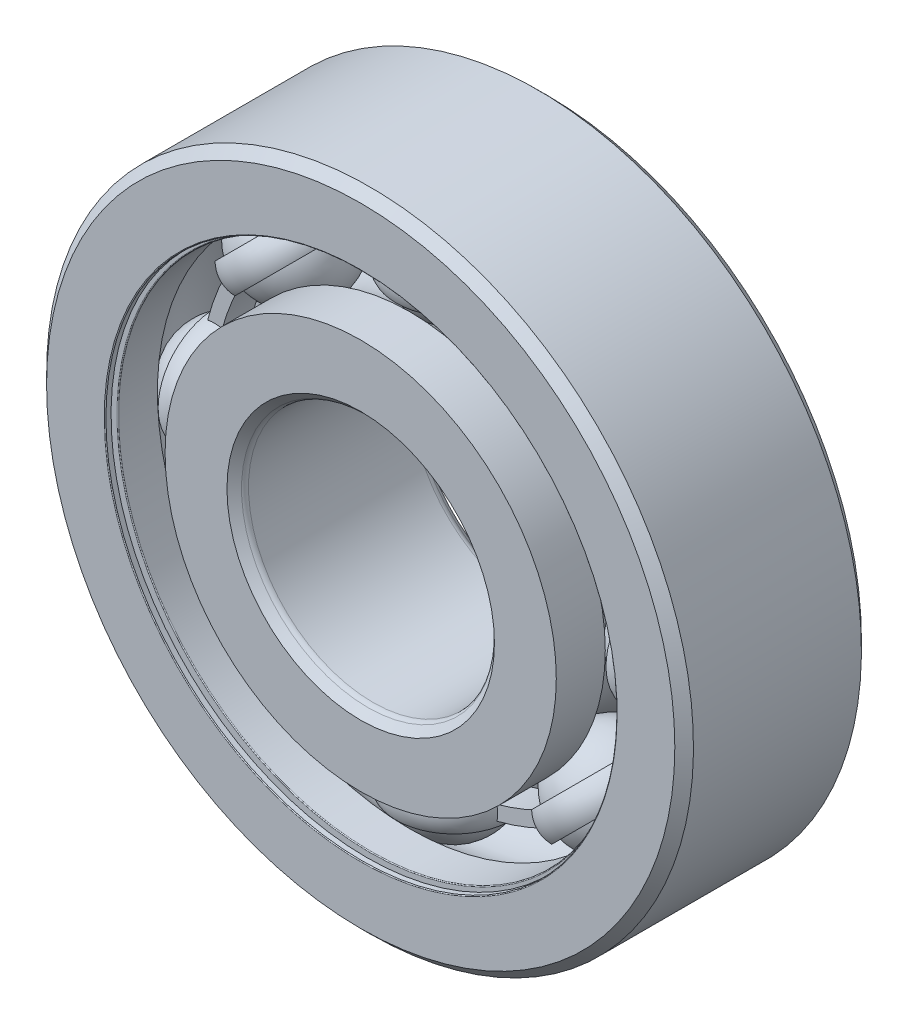
SolidWorks part; units mm, degrees
ref_plane "Front Plane" through (0, 0, 0) normal (0, 0, 1) x (1, 0, 0)
ref_plane "Top Plane" through (0, 0, 0) normal (0, 1, 0) x (1, 0, 0)
ref_plane "Right Plane" through (0, 0, 0) normal (1, 0, 0) x (0, 0, -1)
sketch "Sketch1" plane through (0, 0, 0) normal (0, 0, 1) x (1, 0, 0)
  line L0 (-26, 0) -> (26, 0) construction
  line L1 (-10, 0) -> (10, 0) construction
  circle A0 centre (0, 0) radius 10 construction
  circle A1 centre (0, 0) radius 26 construction
  point P3 (0, 0)
  point P6 (0, 0)
  point P7 (0, -10)
  point P11 (0, -26)
  point P12 (0, 10)
  point P13 (0, 26)
  dimension "OD" = 52
  dimension "ID" = 20
sketch "Sketch2" plane through (0, 0, 0) normal (1, 0, 0) x (0, 0, -1)
  line L0 (-7.5, 26) -> (7.5, 26) construction
  line L1 (0, 26) -> (0, -26) construction
  line L2 (6.75, 26) -> (-6.75, 26)
  line L3 (-6.75, 26) -> (-7.5, 25.25)
  line L4 (-7.5, 25.25) -> (-7.5, 20.2769)
  line L5 (-7.5, 20.2769) -> (-3.5625, 20.2769)
  line L6 (7.5, 20.2769) -> (3.5625, 20.2769)
  line L7 (7.5, 25.25) -> (7.5, 20.2769)
  line L8 (6.75, 26) -> (7.5, 25.25)
  line L9 (0, 26) -> (0, 18) construction
  line L10 (0, 18) -> (0, 10) construction
  line L11 (0, 26) -> (0, -26) construction
  line L12 (-7.5, 0) -> (7.5, 0) construction
  line L13 (7.5, 10) -> (-7.5, 10) construction
  line L14 (0, 22.228) -> (0, 13.772) construction
  line L15 (-7.5, -10) -> (7.5, -10) construction
  line L16 (-7.5, -10) -> (-7.5, 10) construction
  line L17 (7.5, 26) -> (7.5, -26) construction
  arc A0 (-3.5625, 20.2769) -> (3.5625, 20.2769) centre (0, 18) cw
  circle A1 centre (0, 18) radius 4.228 construction
  point P14 (0, 10)
  point P17 (0, 0)
  point P21 (0, 26)
  point P29 (0, 10)
  point P30 (0, -10)
  point P35 (0, 22.228)
  dimension "Approx. Ball Dia." = 8.456
  dimension "Width" = 15
  dimension "D1" = 45
  dimension "D2" = 0.75
  dimension "D3" = 7.125
  dimension "D4" = 2.2769
  dimension "For Shaft Diameter" = 20
  dimension "For Housing ID" = 52
sketch "Sketch3" plane through (0, 0, 0) normal (1, 0, 0) x (0, 0, -1)
  line L0 (6.75, 26) -> (7.5, 25.25) construction
  line L1 (7.5, 25.25) -> (7.5, 20.2769) construction
  line L2 (7.5, 20.2769) -> (3.5625, 20.2769) construction
  line L3 (-7.5, 20.2769) -> (-3.5625, 20.2769) construction
  line L4 (-7.5, 25.25) -> (-7.5, 20.2769) construction
  line L5 (-6.75, 26) -> (-7.5, 25.25) construction
  line L6 (6.75, 26) -> (-6.75, 26) construction
  line L7 (6.75, 26) -> (7.5, 25.25)
  line L8 (7.5, 25.25) -> (7.5, 20.2769)
  line L9 (7.5, 20.2769) -> (3.5625, 20.2769)
  line L10 (-7.5, 20.2769) -> (-3.5625, 20.2769)
  line L11 (-7.5, 25.25) -> (-7.5, 20.2769)
  line L12 (-6.75, 26) -> (-7.5, 25.25)
  line L13 (6.75, 26) -> (-6.75, 26)
  arc A0 (3.5625, 20.2769) -> (-3.5625, 20.2769) centre (0, 18) ccw construction
  arc A1 (3.5625, 20.2769) -> (-3.5625, 20.2769) centre (0, 18) ccw
revolve "Revolve1" add sketch "Sketch3" angle 360 about L12
sketch "Sketch8" plane through (0, 0, 0) normal (1, 0, 0) x (0, 0, -1)
  line L0 (-7.5, 20.2769) -> (-3.5625, 20.2769) construction
  line L1 (-7.02, 20.2769) -> (-6.75, 20.2769)
  line L2 (-7.02, 20.2769) -> (-7.02, 22.1846) construction
  line L3 (-7.02, 22.1846) -> (-6.75, 22.1846)
  line L4 (-6.75, 20.2769) -> (-6.75, 22.1846)
  line L5 (7.5, 20.2769) -> (3.5625, 20.2769) construction
  line L6 (6.75, 20.2769) -> (7.02, 20.2769)
  line L7 (6.75, 20.2769) -> (6.75, 22.1846)
  line L8 (6.75, 22.1846) -> (7.02, 22.1846)
  line L9 (7.02, 20.2769) -> (7.02, 22.1846) construction
  line L10 (-6.75, 22.1846) -> (6.75, 22.1846) construction
  line L11 (0, 26) -> (0, -26) construction
  line L12 (-7.02, 22.1846) -> (-7.02, 24.0923) construction
  line L13 (-7.02, 24.0923) -> (-7.02, 26) construction
  line L14 (-7.5, 26) -> (7.5, 26) construction
  line L15 (-7.02, 20.2769) -> (-7.5, 20.2769)
  line L16 (-7.5, 20.2769) -> (-7.5, 20.5469)
  line L17 (-7.5, 25.25) -> (-7.5, 20.2769) construction
  line L18 (-7.5, 20.5469) -> (-7.02, 20.5469)
  line L19 (-7.02, 20.5469) -> (-7.02, 22.1846)
  line L20 (7.02, 20.2769) -> (7.5, 20.2769)
  line L21 (7.5, 20.2769) -> (7.5, 20.5469)
  line L22 (7.5, 25.25) -> (7.5, 20.2769) construction
  line L23 (7.5, 20.5469) -> (7.02, 20.5469)
  line L24 (7.02, 20.5469) -> (7.02, 22.1846)
  point P12 (0, 22.1846)
  dimension "D1" = 13.5
  dimension "D2" = 0.27
revolve "Cut-Revolve1" cut sketch "Sketch8" angle 360 about L12
sketch "Sketch4" plane through (0, 0, 0) normal (1, 0, 0) x (0, 0, -1)
  line L0 (0, 26) -> (0, -26) construction
  line L1 (0, 26) -> (0, -26) construction
  line L2 (-6.75, 10) -> (-7.5, 10.75)
  line L3 (-7.5, 10.75) -> (-7.5, 15.7231)
  line L5 (-7.5, 15.7231) -> (-3.5625, 15.7231)
  line L6 (-6.75, 10) -> (6.75, 10)
  line L8 (6.75, 10) -> (7.5, 10.75)
  line L10 (7.5, 10.75) -> (7.5, 15.7231)
  line L11 (7.5, 15.7231) -> (3.5625, 15.7231)
  line L12 (-7.5, 25.25) -> (-7.5, 20.2769) construction
  line L13 (6.75, 26) -> (7.5, 25.25) construction
  line L15 (7.5, -25.25) -> (7.5, 25.25) construction
  line L16 (6.75, 26) -> (6.75, -26) construction
  arc A1 (3.5625, 15.7231) -> (-3.5625, 15.7231) centre (0, 18) cw
  circle A2 centre (0, 18) radius 4.228 construction
  point P1 (0, 10)
revolve "Revolve2" add sketch "Sketch4" angle 360 about L12
sketch "Sketch5" plane through (0, 0, 0) normal (1, 0, 0) x (0, 0, -1)
  line L0 (-4.228, 18) -> (4.228, 18)
  arc A2 (-4.228, 18) -> (4.228, 18) centre (0, 18) cw
  arc A3 (3.5625, 20.2769) -> (-3.5625, 20.2769) centre (0, 18) ccw construction
revolve "Revolve3" add sketch "Sketch5" angle 360 about L0
sketch "Sketch6" plane through (0, 0, 0) normal (1, 0, 0) x (0, 0, -1)
  line L0 (-3.5625, 20.2769) -> (-3.5625, 19.1385) construction
  line L1 (-3.5625, 19.1385) -> (-3.5625, 18) construction
  line L2 (-3.5625, 18) -> (-3.5625, 16.8615) construction
  line L3 (-3.5625, 16.8615) -> (-3.5625, 15.7231) construction
  line L4 (-7.5, 19.1385) -> (-6.9286, 19.1385) construction
  line L5 (-3.5625, 19.1385) -> (-3.5625, 16.8615) construction
  line L7 (-6.9286, 19.1385) -> (-6.3573, 19.1385) construction
  line L8 (-6.3573, 19.1385) -> (-5.7859, 19.1385) construction
  line L10 (0, 26) -> (0, -26) construction
  line L11 (0, 26) -> (0, -26) construction
  line L12 (-7.5, 20.2769) -> (-7.5, 19.1385) construction
  line L13 (-4.6432, 19.1385) -> (-4.0718, 19.1385) construction
  line L14 (-7.5, 25.25) -> (-7.5, -25.25) construction
  line L15 (-7.5, 19.1385) -> (-7.5, 18) construction
  line L16 (-7.5, 18) -> (-7.5, 16.8615) construction
  line L17 (-7.5, 16.8615) -> (-7.5, 15.7231) construction
  line L18 (-5.7859, 19.1385) -> (-5.2145, 19.1385) construction
  line L19 (-5.2145, 19.1385) -> (-4.6432, 19.1385) construction
  line L20 (-4.0718, 19.1385) -> (-4.6432, 19.1385)
  line L21 (-7.5, 16.8615) -> (-6.9286, 16.8615) construction
  line L22 (-6.9286, 16.8615) -> (-6.3573, 16.8615) construction
  line L23 (-6.3573, 16.8615) -> (-5.7859, 16.8615) construction
  line L24 (-5.7859, 16.8615) -> (-5.2145, 16.8615) construction
  line L25 (-5.2145, 16.8615) -> (-4.6432, 16.8615) construction
  line L26 (-4.6432, 16.8615) -> (-4.0718, 16.8615) construction
  line L27 (-4.0718, 16.8615) -> (-4.6432, 16.8615)
  line L28 (-5.2145, 19.1385) -> (-5.2145, 16.8615) construction
  line L30 (-4.9289, 19.1385) -> (-4.9289, 16.8615) construction
  circle A0 centre (0, 18) radius 4.228 construction
  arc A2 (-4.6432, 16.8615) -> (-4.6432, 19.1385) centre (-2.5176, 18) cw
  arc A3 (-4.0718, 19.1385) -> (-4.0718, 16.8615) centre (0, 18) ccw
revolve "Revolve4" add sketch "Sketch6" angle 360 about L11
sketch "Sketch7" plane through (0, 0, 0) normal (0, 0, 1) x (1, 0, 0)
  line L0 (-4.228, 18) -> (4.228, 18) construction
  line L1 (0, 13.772) -> (0, 22.228) construction
  line L2 (0, 0) -> (7.1177, 16.5329) construction
  line L8 (0, 26) -> (0, -26) construction
  line L9 (13.0752, 12.3709) -> (13.9022, 13.1533)
  line L10 (0, 26) -> (0, -26) construction
  line L11 (0, 19.1385) -> (0, 18)
  arc A1 (13.0752, 12.3709) -> (0, 18) centre (0, 0) ccw
  arc A2 (13.9022, 13.1533) -> (0, 19.1385) centre (0, 0) ccw
  dimension "D1" = 46.586
  dimension "D2" = 8.456
extrude "Boss-Extrude1" add sketch "Sketch7" along normal mid plane 2.5
pattern_circular "CirPattern1" count 8 over 360 about axis through (0, 0, 7.5) along (0, 0, -1) of bodies 104 134
pattern_circular "CirPattern2" count 8 over 360 about axis through (0, 0, 7.5) along (0, 0, -1) of "Revolve4", "Boss-Extrude1" reverse direction yes
fillet "Fillet1" radius 0.0675 4 edges at (0, -20.2769, -6.75) (0, -20.5469, -7.5) (0, -20.2769, 6.75) (0, -20.5469, 7.5)
fillet "Fillet2" radius 0.5625 2 edges at (0, -10, -6.75) (0, -10, 6.75)
ref_plane "Plane1" through (7.1177, 16.5329, 0) normal (0.3954, 0.9185, 0) x (0.9185, -0.3954, 0)
sketch "Sketch9" plane through (7.1177, 16.5329, 0) normal (0.3954, 0.9185, 0) x (0.9185, -0.3954, 0)
  line L0 (-3.2344, -1.25) -> (-3.2344, -3.75)
  line L1 (-3.2344, -3.75) -> (-1.4029, -3.75)
  line L2 (-1.4029, -3.75) -> (0, -2.5728)
  line L3 (0, -2.5728) -> (1.4029, -3.75)
  line L4 (1.4029, -3.75) -> (3.2344, -3.75)
  line L5 (3.2344, -3.75) -> (3.2344, -1.25)
  line L6 (3.2344, -1.25) -> (-3.2344, -1.25)
  line L7 (0, -1.25) -> (0, 0) construction
  line L8 (-3.2344, -1.25) -> (-3.2344, 0) construction
  dimension "D1" = 2.5
  dimension "D2" = 1.25
  dimension "D3" = 40
extrude "Boss-Extrude2" [suppressed] add sketch "Sketch9" along normal blind 3.6995 draft 15 and the other way blind 3.6995 draft 10 separate body draft outward yes other way draft outward yes
fillet "Fillet3" [suppressed] radius 0.75
mirror "Mirror1" [suppressed] about plane through (0, 0, 0) normal (0, 0, 1) of bodies 149
pattern_circular "CirPattern3" [suppressed] count 8 over 360 about axis through (0, 0, 7.5) along (0, 0, -1) of bodies 158 149
equation "\"D2@Sketch2\" = \"Width@Sketch2\" * .05"
equation "\"D3@Sketch2\"=\"Width@Sketch2\" * .475"
equation "\"D4@Sketch2\" =  (  (  ( \"OD@Sketch1\" - \"Width@Sketch2\" )  / 2 )  / 3.25 )  / 2.5"
equation "\"D1@Boss-Extrude1\" = \"Width@Sketch2\" / 6"
equation "\"D1@Sketch8\"=\"Width@Sketch2\"*.9"
equation "\"D2@Sketch8\"=\"D1@Sketch8\"*.02"
equation "\"D1@Fillet1\" = \"D2@Sketch8\" * .25"
equation "\"D1@Fillet2\" = \"D2@Sketch2\" * .75"
equation "\"Approx No of Balls\"= ( pi * \"OD@Sketch1\" ) * .4 / \"Approx. Ball Dia.@Sketch2\""
equation "\"D1@CirPattern1\"=\"Approx No of Balls\""
equation "\"D1@Sketch7\"=360/\"Approx No of Balls\""
equation "\"D1@CirPattern2\"=\"Approx No of Balls\""
equation "\"D2@Sketch7\"=\"Approx. Ball Dia.@Sketch2\""
equation "\"D2@Sketch9\"=\"d1@boss-extrude1\"*.5"
equation "\"D1@Sketch9\"=\"D2@Sketch9\"*2"
equation "\"D1@Boss-Extrude2\"=\"Approx. Ball Dia.@Sketch2\"*.4375"
equation "\"D2@Boss-Extrude2\"=\"D1@Boss-Extrude2\""
equation "\"D1@CirPattern3\"=\"Approx No of Balls\""
equation "\"D1@Fillet3\"=\"D1@Sketch9\" * .3"
